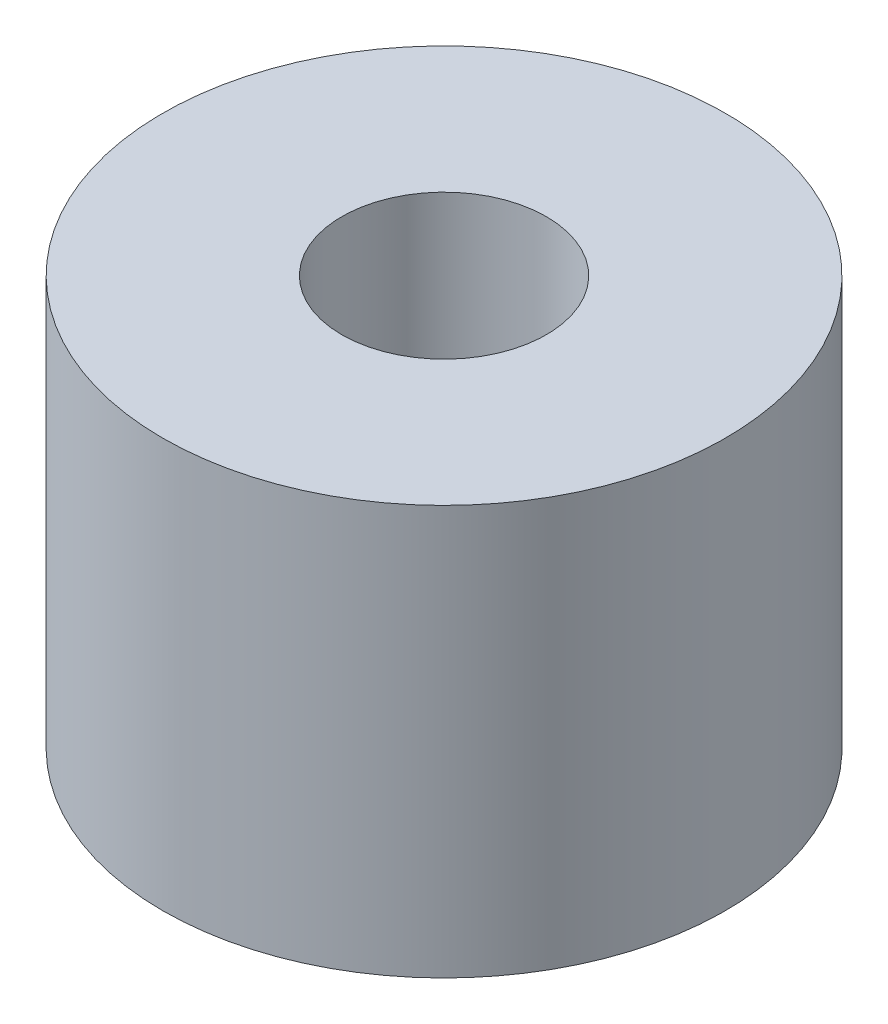
SolidWorks part; units mm, degrees
ref_plane "Спереди" through (0, 0, 0) normal (0, 0, 1) x (1, 0, 0)
ref_plane "Сверху" through (0, 0, 0) normal (0, 1, 0) x (1, 0, 0)
ref_plane "Справа" through (0, 0, 0) normal (1, 0, 0) x (0, 0, -1)
sketch "Эскиз1" plane through (0, 0, 0) normal (0, 1, 0) x (1, 0, 0)
  circle A0 centre (0, 0) radius 2
  circle A1 centre (0, 0) radius 5.5
  dimension "D1" = 4
  dimension "D2" = 11
extrude "Бобышка-Вытянуть1" add sketch "Эскиз1" along normal blind 8
